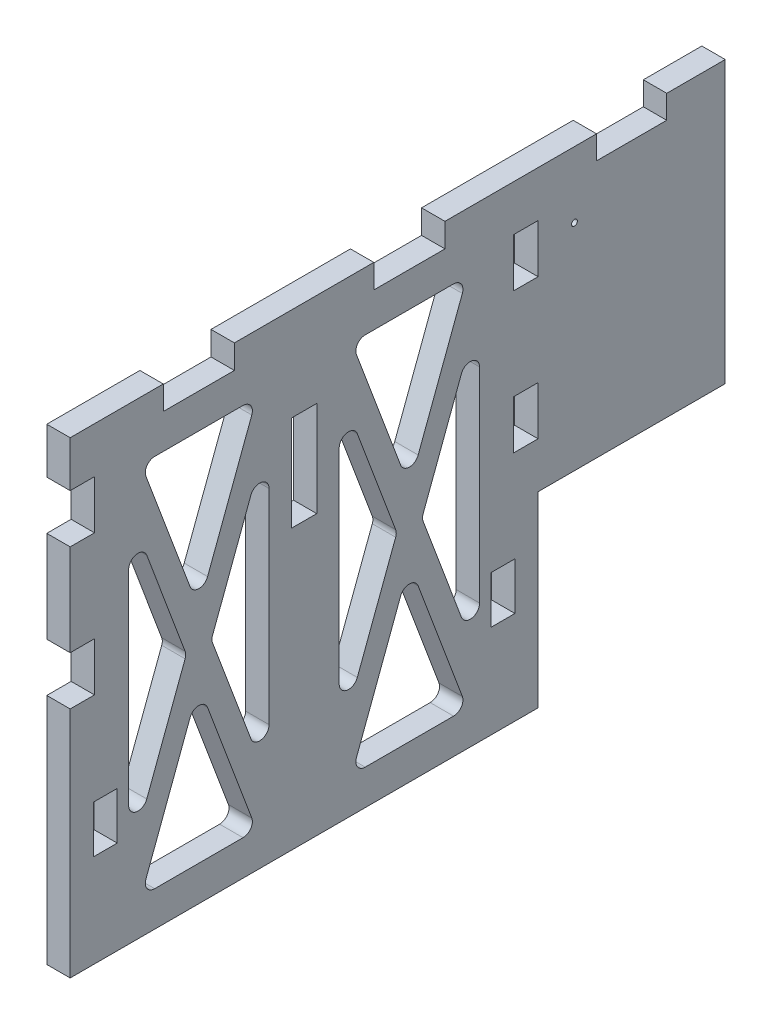
SolidWorks part; units mm, degrees
ref_plane "Front Plane" through (0, 0, 0) normal (0, 0, 1) x (1, 0, 0)
ref_plane "Top Plane" through (0, 0, 0) normal (0, 1, 0) x (1, 0, 0)
ref_plane "Right Plane" through (0, 0, 0) normal (1, 0, 0) x (0, 0, -1)
sketch "Sketch4" plane through (0, 0, 0) normal (1, 0, 0) x (0, 0, -1)
  line L0 (-3.175, 0) -> (-63.5, 0)
  line L3 (-3.175, 0) -> (3.175, 0) construction
  line L5 (3.175, 0) -> (63.5, 0)
  line L6 (63.5, 0) -> (63.5, 32.004)
  line L7 (63.5, 127) -> (38.227, 127)
  line L8 (-63.5, 127) -> (-63.5, 114.554)
  line L9 (0, 0) -> (0, 177.7936) construction
  line L10 (-3.429, 101.6) -> (3.429, 101.6)
  line L11 (-3.175, 101.346) -> (3.175, 101.346) construction
  line L12 (-3.175, 101.346) -> (-3.175, 75.946) construction
  line L13 (-3.175, 75.946) -> (3.175, 75.946) construction
  line L14 (3.175, 101.346) -> (3.175, 75.946) construction
  line L15 (3.429, 101.6) -> (3.429, 75.692)
  line L16 (-3.429, 75.692) -> (3.429, 75.692)
  line L17 (-3.429, 101.6) -> (-3.429, 75.692)
  line L18 (-63.5, 63.5) -> (-57.15, 63.5) construction
  line L19 (-57.15, 63.5) -> (-57.15, 76.2) construction
  line L20 (-57.15, 76.2) -> (-63.5, 76.2) construction
  line L21 (-63.5, 101.6) -> (-57.15, 101.6) construction
  line L22 (-57.15, 101.6) -> (-57.15, 114.3) construction
  line L23 (-57.15, 114.3) -> (-63.5, 114.3) construction
  line L24 (-63.5, 101.346) -> (-63.5, 76.454)
  line L25 (-63.5, 63.246) -> (-63.5, 38.354)
  line L32 (63.5, 114.554) -> (63.5, 127)
  line L34 (-63.5, 101.346) -> (-56.896, 101.346)
  line L35 (-56.896, 101.346) -> (-56.896, 114.554)
  line L36 (-56.896, 114.554) -> (-63.5, 114.554)
  line L37 (-63.5, 63.246) -> (-56.896, 63.246)
  line L38 (-56.896, 63.246) -> (-56.896, 76.454)
  line L39 (-56.896, 76.454) -> (-63.5, 76.454)
  line L40 (57.15, 114.3) -> (63.5, 114.3) construction
  line L41 (57.15, 101.6) -> (57.15, 114.3) construction
  line L42 (63.5, 101.6) -> (57.15, 101.6) construction
  line L43 (57.15, 76.2) -> (63.5, 76.2) construction
  line L44 (57.15, 63.5) -> (57.15, 76.2) construction
  line L45 (63.5, 63.5) -> (57.15, 63.5) construction
  line L46 (56.896, 76.454) -> (63.5, 76.454)
  line L47 (56.896, 63.246) -> (56.896, 76.454)
  line L48 (63.5, 63.246) -> (56.896, 63.246)
  line L49 (56.896, 114.554) -> (63.5, 114.554)
  line L50 (56.896, 101.346) -> (56.896, 114.554)
  line L51 (63.5, 101.346) -> (56.896, 101.346)
  line L52 (63.5, 101.346) -> (63.5, 76.454)
  line L53 (-18.923, 127) -> (-18.923, 120.523)
  line L59 (-19.05, 127) -> (-19.05, 120.65) construction
  line L60 (-19.05, 120.65) -> (-38.1, 120.65) construction
  line L61 (-38.1, 127) -> (-38.1, 120.65) construction
  line L62 (-18.923, 120.523) -> (-38.227, 120.523)
  line L63 (-38.227, 127) -> (-38.227, 120.523)
  line L64 (38.227, 127) -> (38.227, 120.523)
  line L65 (18.923, 120.523) -> (38.227, 120.523)
  line L66 (18.923, 127) -> (18.923, 120.523)
  line L67 (18.923, 127) -> (-18.923, 127)
  line L68 (-38.227, 127) -> (-63.5, 127)
  line L69 (63.5, 44.704) -> (63.5, 32.004)
  line L70 (50.8, 38.1) -> (50.8, 25.4) construction
  line L71 (57.15, 25.4) -> (50.8, 25.4) construction
  line L72 (57.15, 38.1) -> (57.15, 25.4) construction
  line L73 (-57.2262, 38.1762) -> (-50.7238, 38.1762)
  line L74 (-57.15, 38.1) -> (-50.8, 38.1) construction
  line L75 (-57.15, 38.1) -> (-57.15, 25.4) construction
  line L76 (0, 32.258) -> (6.35, 32.258) construction
  line L77 (57.15, 38.1) -> (50.8, 38.1) construction
  line L78 (57.2262, 38.1762) -> (57.2262, 25.3238)
  line L79 (57.2262, 25.3238) -> (50.7238, 25.3238)
  line L80 (-57.15, 25.4) -> (-50.8, 25.4) construction
  line L81 (-50.8, 38.1) -> (-50.8, 25.4) construction
  line L82 (-50.7238, 38.1762) -> (-50.7238, 25.3238)
  line L83 (-0.254, 32.512) -> (6.604, 32.512)
  line L84 (-63.5, 25.654) -> (-63.5, 0)
  line L85 (63.5, 44.704) -> (63.5, 63.246)
  line L86 (-63.5, 38.354) -> (-63.5, 25.654)
  line L87 (-57.2262, 25.3238) -> (-50.7238, 25.3238)
  line L88 (-57.2262, 38.1762) -> (-57.2262, 25.3238)
  line L89 (50.7238, 38.1762) -> (50.7238, 25.3238)
  line L90 (57.2262, 38.1762) -> (50.7238, 38.1762)
  line L91 (-3.175, 0) -> (3.175, 0)
  dimension "D3" = 60.325
  dimension "D4" = 127
  dimension "D5" = 6.35
  dimension "D6" = 25.4
  dimension "D8" = 25.4
  dimension "D9" = 12.7
  dimension "D10" = 12.7
  dimension "D11" = 6.35
  dimension "D12" = 25.4
  dimension "D15" = 25.4
  dimension "D16" = 19.05
  dimension "D17" = 6.35
  dimension "D19" = 6.35
  dimension "D20" = 12.7
  dimension "D21" = 25.4
  dimension "D22" = 6.35
  dimension "D24" = 127
  dimension "D7" = 0.254
  dimension "D13" = 0.254
  dimension "D14" = 0.254
  dimension "D18" = 0.127
  dimension "D23" = 0.0762
extrude "Boss-Extrude1" add sketch "Sketch4" along normal blind 6.35 contours L85 L48 L47 L46 L52 L51 L50 L49 L32 L7 L64 L65 L66 L67 L53 L62 L63 L68 L8 L36 L35 L34 L24 L39 L38 L37 L25 L73 L84 L0 L5 L6 L78 L17 L10 L15 L16 region at (0, 61.9793, 0)
sketch "Sketch5" plane through (6.35, 0, 0) normal (1, 0, 0) x (0, 0, -1)
  line L1 (-47.625, 111.125) -> (47.625, 111.125)
  line L2 (-47.625, 111.125) -> (-47.625, 9.525)
  line L3 (-47.625, 9.525) -> (47.625, 9.525)
  line L4 (47.625, 111.125) -> (47.625, 9.525)
  line L8 (0, 111.125) -> (0, 9.525) construction
  line L10 (-9.525, 111.125) -> (-9.525, 9.525)
  line L12 (9.525, 111.125) -> (9.525, 9.525)
  line L13 (9.525, 9.525) -> (47.625, 111.125) construction
  line L14 (6.5522, 10.6398) -> (44.6522, 112.2398)
  line L15 (12.4978, 8.4102) -> (50.5978, 110.0102)
  line L16 (47.625, 9.525) -> (9.525, 111.125) construction
  line L17 (44.6522, 8.4102) -> (6.5522, 110.0102)
  line L18 (50.5978, 10.6398) -> (12.4978, 112.2398)
  line L19 (-9.525, 9.525) -> (-47.625, 111.125) construction
  line L20 (-6.5522, 10.6398) -> (-44.6522, 112.2398)
  line L21 (-12.4978, 8.4102) -> (-50.5978, 110.0102)
  line L22 (-47.625, 9.525) -> (-9.525, 111.125) construction
  line L23 (-44.6522, 8.4102) -> (-6.5522, 110.0102)
  line L24 (-50.5978, 10.6398) -> (-12.4978, 112.2398)
  line L25 (63.5, 0) -> (63.5, 63.246) construction
  line L26 (63.5, 127) -> (38.227, 127) construction
  line L27 (-63.5, 63.246) -> (-63.5, 0) construction
  line L28 (63.5, 0) -> (-63.5, 0) construction
  arc A0 (6.5522, 10.6398) -> (12.4978, 8.4102) centre (9.525, 9.525) ccw
  arc A1 (50.5978, 110.0102) -> (44.6522, 112.2398) centre (47.625, 111.125) ccw
  arc A2 (44.6522, 8.4102) -> (50.5978, 10.6398) centre (47.625, 9.525) ccw
  arc A3 (12.4978, 112.2398) -> (6.5522, 110.0102) centre (9.525, 111.125) ccw
  arc A4 (-6.5522, 10.6398) -> (-12.4978, 8.4102) centre (-9.525, 9.525) cw
  arc A5 (-50.5978, 110.0102) -> (-44.6522, 112.2398) centre (-47.625, 111.125) cw
  arc A6 (-44.6522, 8.4102) -> (-50.5978, 10.6398) centre (-47.625, 9.525) cw
  arc A7 (-12.4978, 112.2398) -> (-6.5522, 110.0102) centre (-9.525, 111.125) cw
  point P18 (28.575, 60.325)
  point P23 (28.575, 60.325)
  point P28 (-28.575, 60.325)
  point P33 (-28.575, 60.325)
  dimension "D6" = 3.175
  dimension "D1" = 15.875
  dimension "D2" = 15.875
  dimension "D3" = 15.875
  dimension "D4" = 9.525
  dimension "D5" = 19.05
extrude "Cut-Extrude1" cut sketch "Sketch5" against normal through all contours L2 L24 L21 | L20 L24 L1 | L23 L3 L21 | L14 L17 L12 | L18 L14 L1 | L18 L4 L15 | L3 L17 L15 | L23 L20 L10 region at (6.35, 97.2058, 28.575) region at (6.35, 60.325, 42.4053) region at (6.35, 60.325, 14.7447) region at (6.35, 23.4442, 28.575) region at (6.35, 97.2058, -28.575) region at (6.35, 60.325, -14.7447) region at (6.35, 60.325, -42.4053) region at (6.35, 23.4442, -28.575)
fillet "Fillet1" radius 2.54 24 edges at (3.175, 51.2826, 28.575) (3.175, 9.525, 12.9159) (3.175, 9.525, 44.2341) (3.175, 102.0826, 9.525) (3.175, 18.5674, 9.525) (3.175, 60.325, 25.1841) (3.175, 51.2826, -28.575) (3.175, 9.525, -44.2341) (3.175, 9.525, -12.9159) (3.175, 60.325, -31.9659) (3.175, 102.0826, -47.625) (3.175, 18.5674, -47.625) (3.175, 60.325, 31.9659) (3.175, 18.5674, 47.625) (3.175, 102.0826, 47.625) (3.175, 111.125, -12.9159) (3.175, 111.125, -44.2341) (3.175, 69.3674, -28.575) (3.175, 111.125, 12.9159) (3.175, 69.3674, 28.575) (3.175, 102.0826, -9.525) (3.175, 60.325, -25.1841) (3.175, 18.5674, -9.525) (3.175, 111.125, 44.2341)
fillet "Fillet2" [suppressed] radius 2.54
ref_plane "Plane1" through (0, 88.0753, -47.625) normal (0, -1, 0) x (-1, 0, 0)
sketch "Sketch7" plane through (0, 0, 0) normal (-1, 0, 0) x (0, 0, 1)
  line L0 (-63.5, 114.554) -> (-63.5, 127) construction
  line L1 (-63.5, 127) -> (-114.3, 127)
  line L2 (-63.5, 127) -> (-63.5, 50.8)
  line L3 (-63.5, 50.8) -> (-114.3, 50.8)
  line L4 (-114.3, 127) -> (-114.3, 50.8)
  line L5 (-63.5, 127) -> (-38.227, 127) construction
  line L6 (-88.9, 127) -> (-88.9, 106.193) construction
  line L7 (-98.425, 127) -> (-79.375, 127)
  line L8 (-98.425, 127) -> (-98.425, 120.65)
  line L9 (-98.425, 120.65) -> (-79.375, 120.65)
  line L10 (-79.375, 127) -> (-79.375, 120.65)
  dimension "D1" = 50.8
  dimension "D2" = 76.2
  dimension "D3" = 6.35
  dimension "D4" = 19.05
extrude "Boss-Extrude2" add sketch "Sketch7" against normal blind 6.35 contours L1 L10 L9 L8 L4 L3 L2 region at (0, 87.7734, -88.9)
sketch "Sketch8" plane through (6.35, 0, 0) normal (1, 0, 0) x (0, 0, -1)
  circle A0 centre (73.37, 109.0918) radius 0.7937
  point P2 (73.37, 109.0918)
  dimension "D1" = 1.5875
extrude "Cut-Extrude2" cut sketch "Sketch8" against normal through all
